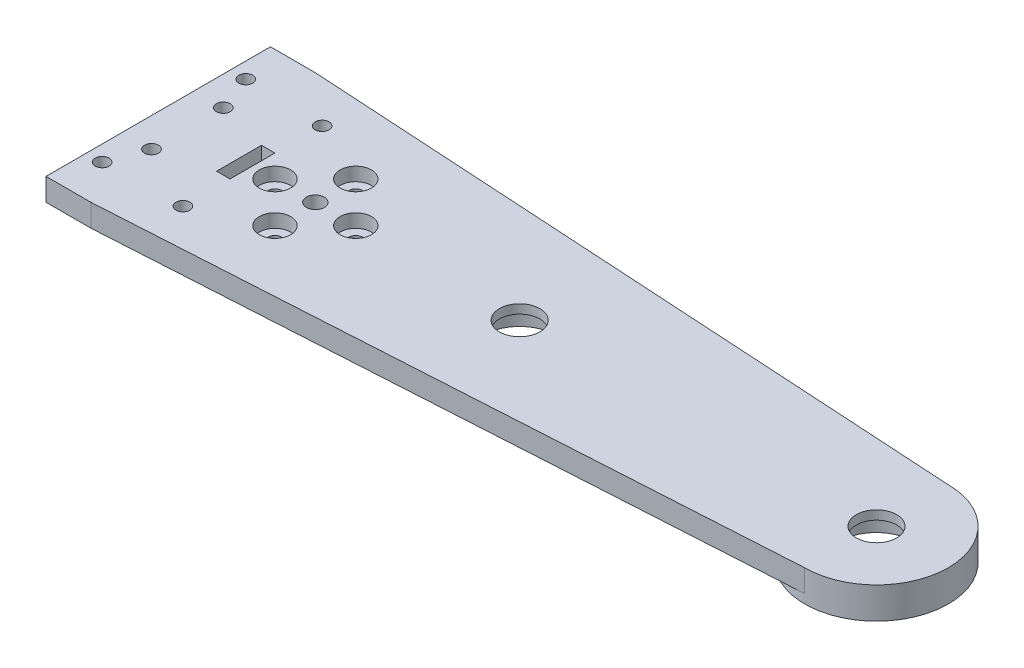
SolidWorks part; units mm, degrees
ref_plane "Front Plane" through (0, 0, 0) normal (0, 0, 1) x (1, 0, 0)
ref_plane "Top Plane" through (0, 0, 0) normal (0, 1, 0) x (1, 0, 0)
ref_plane "Right Plane" through (0, 0, 0) normal (1, 0, 0) x (0, 0, -1)
sketch "Sketch28" plane through (-32, 0, 0) normal (0, -1, 0) x (0, 0, 1)
  line L1 (0, -20) -> (0, -65.5) construction
  line L2 (-8, 8.5) -> (8, 8.5) construction
  line L3 (0, 15) -> (0, -3) construction
  line L8 (-25, 15) -> (25, 15)
  line L12 (25, 15) -> (25, 5)
  line L13 (-25, 15) -> (-25, 5)
  line L14 (-25, 5) -> (-16, -145)
  line L15 (16, -145) -> (25, 5)
  line L16 (-25, 5) -> (-25, 8.5) construction
  line L17 (-25, 8.5) -> (-8, 8.5) construction
  line L18 (-25, 15) -> (-25, 11.5) construction
  line L19 (-25, 11.5) -> (-16, 11.5) construction
  line L20 (-16, 11.5) -> (16, 11.5) construction
  line L21 (-5, -3) -> (5, -3)
  line L26 (5, -3) -> (5, -6)
  line L27 (5, -6) -> (-5, -6)
  line L28 (-5, -6) -> (-5, -3)
  line L29 (-5, -3) -> (-15.5, -3) construction
  line L30 (-15.5, -3) -> (-15.5, -6) construction
  line L31 (5, -3) -> (15.5, -3) construction
  line L32 (15.5, -3) -> (15.5, -6) construction
  line L33 (0, -20) -> (0, -6) construction
  line L34 (0, -65.5) -> (0, -145) construction
  circle A7 centre (8, 8.5) radius 1.55
  circle A8 centre (-8, 8.5) radius 1.55
  circle A9 centre (16, 11.5) radius 1.55
  circle A10 centre (-16, 11.5) radius 1.55
  circle A13 centre (-15.5, -6) radius 1.55
  circle A14 centre (15.5, -6) radius 1.55
  circle A15 centre (0, -20) radius 12.5 construction
  circle A19 centre (0, -65.5) radius 4.5
  circle A20 centre (0, -20) radius 2
  circle A21 centre (0, -145) radius 4.5
  arc A22 (-16, -145) -> (16, -145) centre (0, -145) ccw
  circle A23 centre (0, -20) radius 9 construction
  circle A24 centre (-9, -20) radius 1.55
  circle A25 centre (0, -11) radius 1.55
  circle A26 centre (9, -20) radius 1.55
  circle A27 centre (0, -29) radius 1.55
  point P13 (0, 15)
  point P27 (0, -3)
  point P51 (0, -20)
extrude "Boss-Extrude10" add sketch "Sketch28" along normal blind 5
sketch "Sketch29" plane through (0, -5, 0) normal (0, -1, 0) x (1, 0, 0)
  circle A0 centre (33.5, 0) radius 16
  circle A5 centre (113, 0) radius 16
extrude "Boss-Extrude11" add sketch "Sketch29" along normal blind 2
sketch "Sketch30" plane through (0, -7, 0) normal (0, -1, 0) x (1, 0, 0)
  circle A0 centre (33.5, 0) radius 8.2
  circle A1 centre (113, 0) radius 8.2
extrude "Cut-Extrude1" cut sketch "Sketch30" against normal blind 5
sketch "Sketch31" plane through (0, 0, 0) normal (0, 1, 0) x (1, 0, 0)
  circle A0 centre (-12, 9) radius 3.5
  circle A1 centre (-3, 0) radius 3.5
  circle A2 centre (-12, -9) radius 3.5
  circle A3 centre (-21, 0) radius 3.5
  point P12 (-12, 0)
extrude "Cut-Extrude2" cut sketch "Sketch31" against normal blind 3
